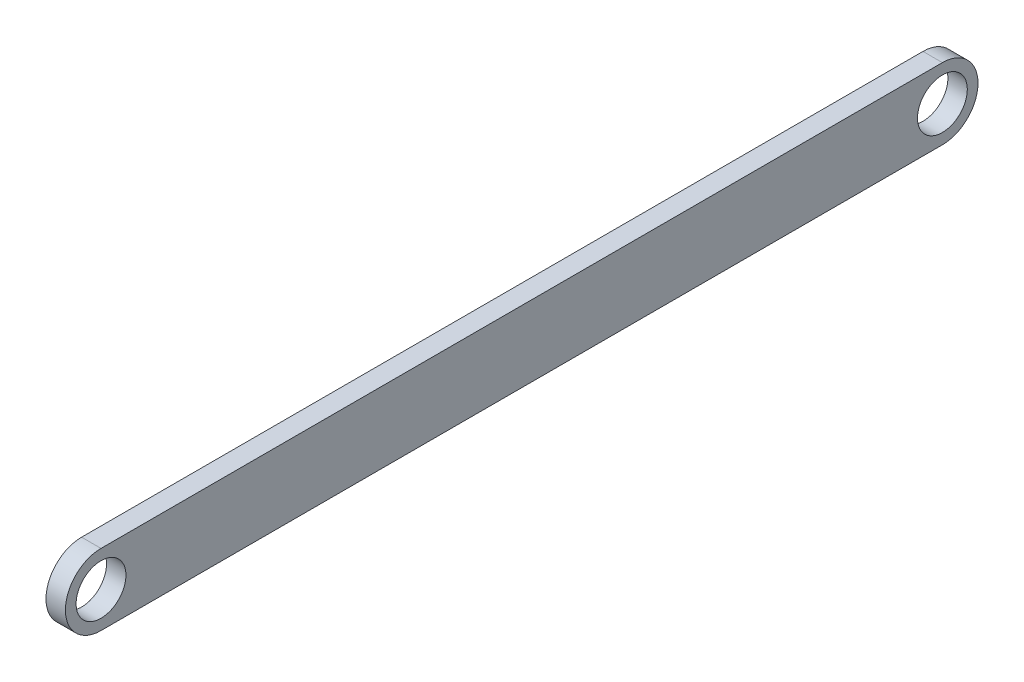
SolidWorks part; units mm, degrees
ref_plane "Front Plane" through (0, 0, 0) normal (0, 0, 1) x (1, 0, 0)
ref_plane "Top Plane" through (0, 0, 0) normal (0, 1, 0) x (1, 0, 0)
ref_plane "Right Plane" through (0, 0, 0) normal (1, 0, 0) x (0, 0, -1)
sketch "Sketch1" plane through (0, 0, 0) normal (1, 0, 0) x (0, 0, -1)
  line L0 (-89.172, -2.2228) -> (40.828, -2.2228) construction
  line L1 (-89.172, 3.2772) -> (40.828, 3.2772)
  line L2 (-89.172, 3.2772) -> (-89.172, -7.7228)
  line L3 (-89.172, -7.7228) -> (40.828, -7.7228)
  line L4 (40.828, 3.2772) -> (40.828, -7.7228)
  circle A0 centre (-89.172, -2.2228) radius 3.85
  circle A1 centre (-89.172, -2.2228) radius 5.5
  circle A2 centre (40.828, -2.2228) radius 3.85
  circle A3 centre (40.828, -2.2228) radius 5.5
  dimension "D1" = 7.7
  dimension "D3" = 130
  dimension "D4" = 11
extrude "Boss-Extrude3" add sketch "Sketch1" along normal blind 3 contours L0 A1 L3 A3 | A1 L0 A3 L1 | A0 L0 A1 L1 L2 | L0 A0 L2 L3 A1 | L2 A0 | L0 L2 A0 | L2 L0 A0 | L1 A1 L3 L2 A0 | L4 A2 | L0 A2 L4 | A2 L0 L4 | A3 L0 A2 L4 L1 | L3 A3 L1 L4 A2 | L0 A3 L3 L4 A2 region at (0, -0.5889, 87.538) region at (0, -2.2228, 90.8059) region at (0, -3.8568, 87.538) region at (0, 0.7843, 86.1649) region at (0, -5.2299, 86.1649) region at (0, -2.2228, 93.1449) region at (0, 0.5568, 24.172) region at (0, -5.0024, 24.172) region at (0, 0.7843, -37.821) region at (0, -5.2299, -37.821) region at (0, 1.5793, -44.6302) region at (0, -0.5889, -39.1941) region at (0, -3.8568, -39.1941) region at (0, -2.2228, -42.462)
extrude "Cut-Extrude2" cut sketch "Sketch1<7>" along normal through all contours L2 A0 | L2 L0 A0 | L0 L2 A0 | L4 A2 | L0 A2 L4 | A2 L0 L4 region at (0, -0.5889, 87.538) region at (0, -2.2228, 90.8059) region at (0, -3.8568, 87.538) region at (0, -0.5889, -39.1941) region at (0, -3.8568, -39.1941) region at (0, -2.2228, -42.462)
sketch "Sketch1<7>" plane through (0, 0, 0) normal (1, 0, 0) x (0, 0, -1) same geometry as "Sketch1"
